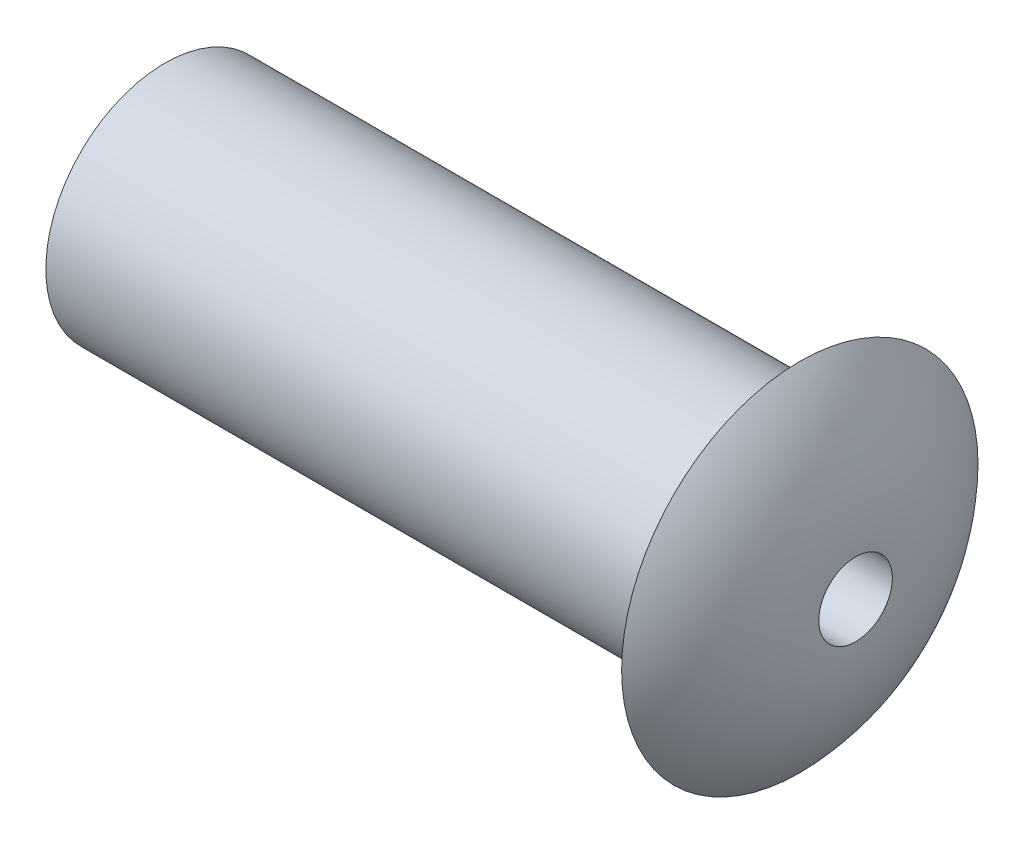
SolidWorks part; units mm, degrees
ref_plane "Front Plane" through (0, 0, 0) normal (0, 0, 1) x (1, 0, 0)
ref_plane "Top Plane" through (0, 0, 0) normal (0, 1, 0) x (1, 0, 0)
ref_plane "Right Plane" through (0, 0, 0) normal (1, 0, 0) x (0, 0, -1)
sketch "Sketch1" plane through (82.9692, 0, 0) normal (1, 0, 0) x (0, 0, -1)
  circle A0 centre (-223, 21.8) radius 1.875
  dimension "D1" = 3.75
extrude "Boss-Extrude1" add sketch "Sketch1" against normal blind 10
ref_axis "Axis1" through (72.9692, 21.8, 223) along (1, 0, 0)
ref_plane "Plane1" through (0, 0, 223) normal (0, 0, 1) x (1, 0, 0)
sketch "Sketch2" plane through (0, 0, 223) normal (0, 0, 1) x (1, 0, 0)
  line L0 (82.9692, 21.8) -> (84.4555, 21.8) construction
  line L1 (82.9692, 19.925) -> (82.9692, 23.675) construction
  line L2 (82.9692, 18.9936) -> (82.9692, 21.8)
  line L4 (83.8475, 21.8) -> (83.8475, 21.2205)
  line L5 (82.9692, -12.2) -> (82.9692, 23.8) construction
  line L6 (82.9692, 18.9936) -> (82.9692, 19.925)
  arc A0 (83.8475, 21.2205) -> (82.9692, 18.9936) centre (80.5852, 21.2205) cw
  point P9 (83.8475, 21.8)
revolve "Revolve1" add sketch "Sketch2" angle 360 about L0 region at (83.3479, 20.6819, 223)
sketch "Sketch3" plane through (83.8475, 0, 0) normal (1, 0, 0) x (0, 0, -1)
  circle A0 centre (-223, 21.8) radius 0.5795 construction
  circle A1 centre (-223, 21.8) radius 0.5795
extrude "Cut-Extrude1" cut sketch "Sketch3" against normal blind 1
